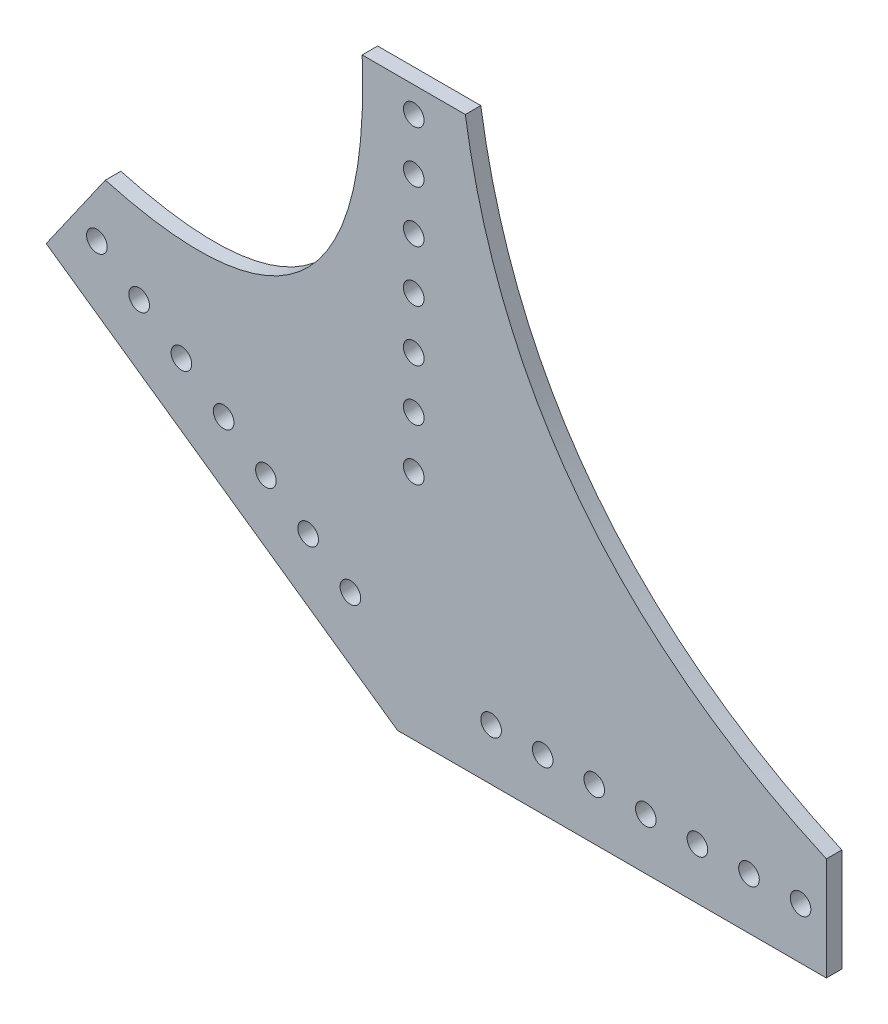
SolidWorks part; units mm, degrees
ref_plane "Front Plane" through (0, 0, 0) normal (0, 0, 1) x (1, 0, 0)
ref_plane "Top Plane" through (0, 0, 0) normal (0, 1, 0) x (1, 0, 0)
ref_plane "Right Plane" through (0, 0, 0) normal (1, 0, 0) x (0, 0, -1)
sketch "Sketch1" plane through (0, 0, 0) normal (0, 0, 1) x (1, 0, 0)
  line L0 (-280.0652, 184.4073) -> (-30.3877, 9.5812)
  line L1 (0, 0) -> (431.8, 0)
  line L2 (0, 0) -> (0, 25.4)
  line L3 (0, 25.4) -> (431.8, 25.4)
  line L4 (431.8, 0) -> (431.8, 25.4)
  line L5 (-280.0652, 184.4073) -> (-265.4964, 205.2137)
  line L6 (-30.3877, 9.5812) -> (-15.8188, 30.3877)
  line L7 (-265.4964, 205.2137) -> (-15.8188, 30.3877)
  line L8 (-25.4, 50.8) -> (0, 50.8)
  line L9 (-25.4, 50.8) -> (-25.4, 355.6)
  line L10 (0, 50.8) -> (0, 355.6)
  line L11 (-25.4, 355.6) -> (0, 355.6)
  line L12 (-225.8432, 161.9445) -> (23.8343, -12.8816) construction
  line L13 (0, 12.7) -> (431.8, 12.7) construction
  line L14 (-12.7, 12.7) -> (-12.7, 105.3379) construction
  line L15 (-12.7, 57.15) -> (-12.7, 69.85) construction
  line L16 (6.35, 12.7) -> (19.05, 12.7) construction
  line L17 (-28.3048, 23.6266) -> (-38.7081, 30.9111) construction
  line L18 (-103.2103, 60.5721) -> (-88.6414, 81.3786)
  line L20 (-25.4, 139.7) -> (0, 139.7)
  line L22 (88.9, 25.4) -> (88.9, 0)
  line L23 (88.9, 0) -> (-16.7043, 0)
  line L24 (-16.7043, 0) -> (-103.2103, 60.5721)
  line L25 (-88.6414, 81.3786) -> (-15.8188, 30.3877) construction
  line L26 (0, 25.4) -> (88.9, 25.4) construction
  line L27 (-25.4, 139.7) -> (-25.4, 50.8) construction
  line L28 (0, 139.7) -> (0, 50.8) construction
  line L29 (0, 0) -> (88.9, 0) construction
  circle A0 centre (-12.7, 57.15) radius 2.54
  circle A1 centre (-12.7, 69.85) radius 2.54
  circle A2 centre (-12.7, 82.55) radius 2.54
  circle A3 centre (-12.7, 95.25) radius 2.54
  circle A4 centre (-12.7, 107.95) radius 2.54
  circle A5 centre (-12.7, 120.65) radius 2.54
  circle A6 centre (-12.7, 133.35) radius 2.54
  circle A7 centre (-12.7, 146.05) radius 2.54
  circle A8 centre (-12.7, 158.75) radius 2.54
  circle A9 centre (-12.7, 171.45) radius 2.54
  circle A10 centre (-12.7, 184.15) radius 2.54
  circle A11 centre (-12.7, 196.85) radius 2.54
  circle A12 centre (-12.7, 209.55) radius 2.54
  circle A13 centre (-12.7, 222.25) radius 2.54
  circle A14 centre (-12.7, 234.95) radius 2.54
  circle A15 centre (-12.7, 247.65) radius 2.54
  circle A16 centre (-12.7, 260.35) radius 2.54
  circle A17 centre (-12.7, 273.05) radius 2.54
  circle A18 centre (-12.7, 285.75) radius 2.54
  circle A19 centre (-12.7, 298.45) radius 2.54
  circle A20 centre (-12.7, 311.15) radius 2.54
  circle A21 centre (-12.7, 323.85) radius 2.54
  circle A22 centre (-12.7, 336.55) radius 2.54
  circle A23 centre (-12.7, 349.25) radius 2.54
  circle A24 centre (6.35, 12.7) radius 2.54
  circle A25 centre (19.05, 12.7) radius 2.54
  circle A26 centre (31.75, 12.7) radius 2.54
  circle A27 centre (44.45, 12.7) radius 2.54
  circle A28 centre (57.15, 12.7) radius 2.54
  circle A29 centre (69.85, 12.7) radius 2.54
  circle A30 centre (82.55, 12.7) radius 2.54
  circle A31 centre (95.25, 12.7) radius 2.54
  circle A32 centre (107.95, 12.7) radius 2.54
  circle A33 centre (120.65, 12.7) radius 2.54
  circle A34 centre (133.35, 12.7) radius 2.54
  circle A35 centre (146.05, 12.7) radius 2.54
  circle A36 centre (158.75, 12.7) radius 2.54
  circle A37 centre (171.45, 12.7) radius 2.54
  circle A38 centre (184.15, 12.7) radius 2.54
  circle A39 centre (196.85, 12.7) radius 2.54
  circle A40 centre (209.55, 12.7) radius 2.54
  circle A41 centre (222.25, 12.7) radius 2.54
  circle A42 centre (234.95, 12.7) radius 2.54
  circle A43 centre (247.65, 12.7) radius 2.54
  circle A44 centre (260.35, 12.7) radius 2.54
  circle A45 centre (273.05, 12.7) radius 2.54
  circle A46 centre (285.75, 12.7) radius 2.54
  circle A47 centre (298.45, 12.7) radius 2.54
  circle A48 centre (311.15, 12.7) radius 2.54
  circle A49 centre (323.85, 12.7) radius 2.54
  circle A50 centre (336.55, 12.7) radius 2.54
  circle A51 centre (349.25, 12.7) radius 2.54
  circle A52 centre (361.95, 12.7) radius 2.54
  circle A53 centre (374.65, 12.7) radius 2.54
  circle A54 centre (387.35, 12.7) radius 2.54
  circle A55 centre (400.05, 12.7) radius 2.54
  circle A56 centre (412.75, 12.7) radius 2.54
  circle A57 centre (425.45, 12.7) radius 2.54
  circle A58 centre (-28.3048, 23.6266) radius 2.54
  circle A59 centre (-38.7081, 30.9111) radius 2.54
  circle A60 centre (-49.1113, 38.1955) radius 2.54
  circle A61 centre (-59.5145, 45.4799) radius 2.54
  circle A62 centre (-69.9178, 52.7643) radius 2.54
  circle A63 centre (-80.321, 60.0487) radius 2.54
  circle A64 centre (-90.7242, 67.3332) radius 2.54
  circle A65 centre (-101.1275, 74.6176) radius 2.54
  circle A66 centre (-111.5307, 81.902) radius 2.54
  circle A67 centre (-121.9339, 89.1864) radius 2.54
  circle A68 centre (-132.3372, 96.4708) radius 2.54
  circle A69 centre (-142.7404, 103.7553) radius 2.54
  circle A70 centre (-153.1436, 111.0397) radius 2.54
  circle A71 centre (-163.5468, 118.3241) radius 2.54
  circle A72 centre (-173.9501, 125.6085) radius 2.54
  circle A73 centre (-184.3533, 132.8929) radius 2.54
  circle A74 centre (-194.7565, 140.1774) radius 2.54
  circle A75 centre (-205.1598, 147.4618) radius 2.54
  circle A76 centre (-215.563, 154.7462) radius 2.54
  circle A77 centre (-225.9662, 162.0306) radius 2.54
  circle A78 centre (-236.3695, 169.315) radius 2.54
  circle A79 centre (-246.7727, 176.5995) radius 2.54
  circle A80 centre (-257.1759, 183.8839) radius 2.54
  circle A81 centre (-267.5792, 191.1683) radius 2.54
  circle A82 centre (-80.321, 60.0487) radius 2.54
  circle A83 centre (-69.9178, 52.7643) radius 2.54
  circle A84 centre (-59.5145, 45.4799) radius 2.54
  circle A85 centre (-49.1113, 38.1955) radius 2.54
  circle A86 centre (-38.7081, 30.9111) radius 2.54
  circle A87 centre (-28.3048, 23.6266) radius 2.54
  circle A88 centre (82.55, 12.7) radius 2.54
  circle A89 centre (-12.7, 133.35) radius 2.54
  circle A90 centre (-90.7242, 67.3332) radius 2.54
  circle A91 centre (69.85, 12.7) radius 2.54
  circle A92 centre (57.15, 12.7) radius 2.54
  circle A93 centre (44.45, 12.7) radius 2.54
  circle A94 centre (31.75, 12.7) radius 2.54
  circle A95 centre (19.05, 12.7) radius 2.54
  circle A96 centre (6.35, 12.7) radius 2.54
  circle A97 centre (-12.7, 120.65) radius 2.54
  circle A98 centre (-12.7, 107.95) radius 2.54
  circle A99 centre (-12.7, 95.25) radius 2.54
  circle A100 centre (-12.7, 82.55) radius 2.54
  circle A101 centre (-12.7, 69.85) radius 2.54
  circle A102 centre (-12.7, 57.15) radius 2.54
  circle A103 centre (-80.321, 60.0487) radius 2.54
  circle A104 centre (-69.9178, 52.7643) radius 2.54
  circle A105 centre (-59.5145, 45.4799) radius 2.54
  circle A106 centre (-49.1113, 38.1955) radius 2.54
  circle A107 centre (-38.7081, 30.9111) radius 2.54
  circle A108 centre (-28.3048, 23.6266) radius 2.54
  spline S0 degree 2 poles (-88.6414, 81.3786) (-22.413, 63.0363) (-25.4, 139.7) knots 0 0 0 1 1 1
  spline S1 degree 2 poles (0, 139.7) (12.336, 59.7959) (88.9, 25.4) knots 0 0 0 1 1 1
  point P12 (-23.1032, 19.9844)
  point P17 (0, 12.7)
  point P19 (-12.7, 12.7)
  point P22 (-12.7, 50.8)
  point P214 (-95.9258, 70.9754)
  dimension "D12" = 5.08
  dimension "D15" = 5.08
  dimension "D19" = 5.08
  dimension "D20" = 6.35
  dimension "D1" = 25.4
  dimension "D2" = 431.8
  dimension "D3" = 25.4
  dimension "D4" = 25.4
  dimension "D5" = 304.8
  dimension "D6" = 304.8
  dimension "D7" = 145
  dimension "D8" = 12.7
  dimension "D9" = 12.7
  dimension "D10" = 38.1
  dimension "D11" = 6.35
  dimension "D14" = 12.7
  dimension "D16" = 6.35
  dimension "D18" = 12.7
  dimension "D21" = 12.7
  dimension "D24" = 6.35
  dimension "D25" = 6.35
  dimension "D26" = 6.35
  dimension "D13" = 24
  dimension "D17" = 34
  dimension "D22" = 24
  dimension "D23" = 7
  dimension "D27" = 7
  dimension "D28" = 7
  dimension "D29" = 7
extrude "Boss-Extrude3" add sketch "Sketch1" along normal blind 3.81 contours S1 L22 L23 L24 L18 S0 L20
extrude "Cut-Extrude6" cut sketch "Sketch1<7>" along normal blind 3.81 contours A64 | A63 | A62 | A61 | A60 | A59 | A58 | A24 | A25 | A26 | A27 | A28 | A29 | A30 | A0 | A1 | A2 | A3 | A4 | A5 | A6
sketch "Sketch1<7>" plane through (0, 0, 0) normal (0, 0, 1) x (1, 0, 0) same geometry as "Sketch1"
